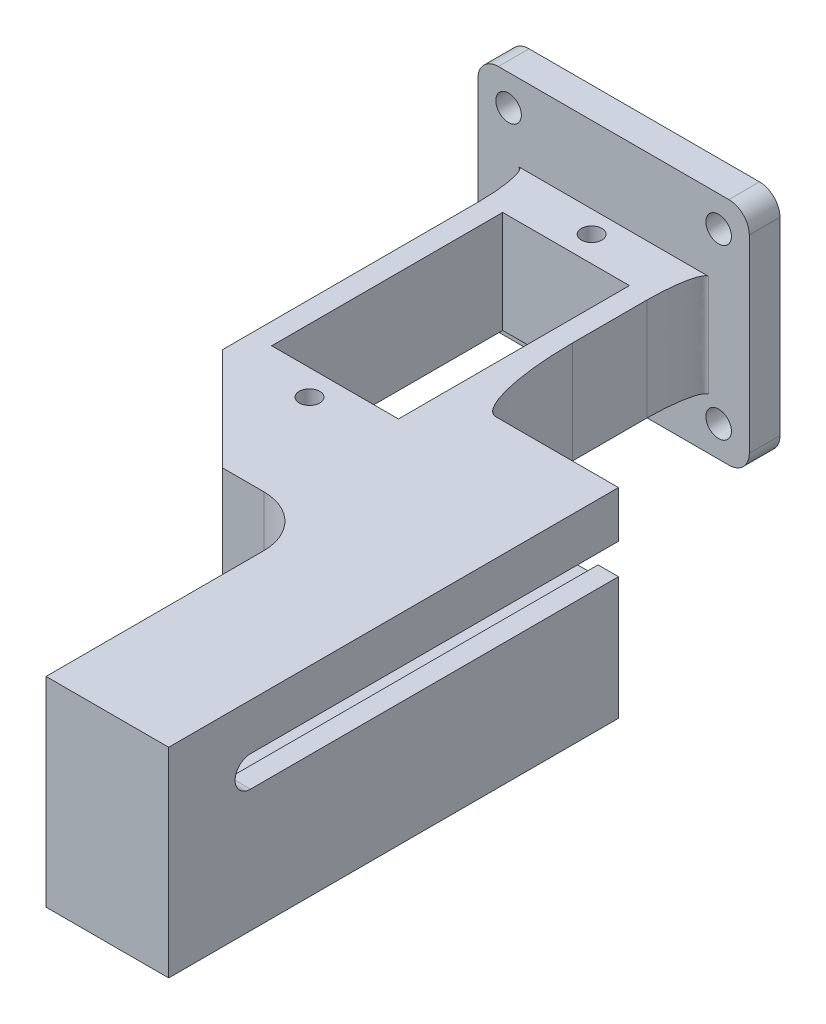
SolidWorks part; units mm, degrees
ref_plane "Front Plane" through (0, 0, 0) normal (0, 0, 1) x (1, 0, 0)
ref_plane "Top Plane" through (0, 0, 0) normal (0, 1, 0) x (1, 0, 0)
ref_plane "Right Plane" through (0, 0, 0) normal (1, 0, 0) x (0, 0, -1)
sketch "Sketch1" plane through (0, 0, 0) normal (0, 0, 1) x (1, 0, 0)
  line L0 (0, 11.25) -> (0, -11.25) construction
  line L1 (-13.275, 0) -> (13.275, 0) construction
  line L2 (-13.275, 9.25) -> (-11.275, 9.25) construction
  line L3 (-11.275, 9.25) -> (-11.275, 11.25) construction
  line L4 (11.275, 11.25) -> (11.275, 9.25) construction
  line L5 (11.275, 9.25) -> (13.275, 9.25) construction
  line L6 (11.275, -11.25) -> (11.275, -9.25) construction
  line L7 (11.275, -9.25) -> (13.275, -9.25) construction
  line L8 (13.275, -9.25) -> (13.275, 9.25)
  line L9 (11.275, 11.25) -> (-11.275, 11.25)
  line L10 (-13.275, 9.25) -> (-13.275, -9.25)
  line L11 (-11.275, -11.25) -> (11.275, -11.25)
  line L12 (-13.275, -9.25) -> (-11.275, -9.25) construction
  line L13 (-11.275, -9.25) -> (-11.275, -11.25) construction
  circle A0 centre (-10.275, 8.25) radius 1.25
  circle A1 centre (10.275, 8.25) radius 1.25
  circle A2 centre (10.275, -8.25) radius 1.25
  circle A3 centre (-10.275, -8.25) radius 1.25
  arc A8 (11.275, -11.25) -> (13.275, -9.25) centre (11.275, -9.25) ccw
  arc A9 (13.275, 9.25) -> (11.275, 11.25) centre (11.275, 9.25) ccw
  arc A10 (-11.275, 11.25) -> (-13.275, 9.25) centre (-11.275, 9.25) ccw
  arc A11 (-13.275, -9.25) -> (-11.275, -11.25) centre (-11.275, -9.25) ccw
  point P15 (0, 0)
  dimension "D3" = 2
  dimension "D4" = 2
  dimension "D5" = 2
  dimension "D6" = 2
  dimension "D7" = 2.5
  dimension "D1" = 26.55
  dimension "D2" = 22.5
  dimension "D8" = 3
  dimension "D9" = 3
extrude "Boss-Extrude1" add sketch "Sketch1" along normal blind 3
sketch "Sketch2" plane through (0, 0, 0) normal (0, 0, -1) x (-1, 0, 0)
  line L0 (11.275, -11.25) -> (-11.275, -11.25) construction
  line L1 (-8.275, 3.75) -> (8.275, 3.75)
  line L2 (-8.275, 3.75) -> (-8.275, -6.25)
  line L3 (-8.275, -6.25) -> (8.275, -6.25)
  line L4 (8.275, 3.75) -> (8.275, -6.25)
  line L5 (-8.275, 3.75) -> (8.275, -6.25) construction
  line L6 (-8.275, -6.25) -> (8.275, 3.75) construction
  line L7 (13.275, 9.25) -> (13.275, -9.25) construction
  point P0 (0, -1.25)
  dimension "D1" = 16.55
  dimension "D2" = 10
  dimension "D3" = 5
  dimension "D4" = 5
extrude "Boss-Extrude2" add sketch "Sketch2" along normal blind 30
sketch "Sketch3" plane through (0, 3.75, 0) normal (0, 1, 0) x (1, 0, 0)
  line L0 (-8.275, 30) -> (1.725, 40)
  line L1 (1.725, 40) -> (8.275, 40)
  line L2 (8.275, 40) -> (8.275, 30)
  line L3 (8.275, 30) -> (-8.275, 30)
  line L4 (8.275, 30) -> (8.275, 0) construction
  dimension "D1" = 10
  dimension "D2" = 45
  dimension "D3" = 6.55
extrude "Boss-Extrude3" add sketch "Sketch3" against normal up to surface (10 mm away) up to face at (0, -6.25, -15)
ref_plane "Plane1" through (0, 0, 1.5) normal (0, 0, 1) x (1, 0, 0)
mirror "Mirror1" about plane through (0, 0, 1.5) normal (0, 0, 1) of "Boss-Extrude3", "Boss-Extrude2"
sketch "Sketch4" plane through (0, -6.25, 0) normal (0, -1, 0) x (1, 0, 0)
  line L5 (8.275, 0) -> (-8.275, 0)
  line L6 (-8.275, 0) -> (-8.275, -30)
  line L7 (-8.275, -30) -> (1.725, -40)
  line L8 (1.725, -40) -> (8.275, -40)
  line L9 (8.275, -40) -> (8.275, 0)
  line L10 (8.275, 0) -> (-8.275, 0)
  line L11 (-8.275, 0) -> (-8.275, -30)
  line L12 (-8.275, -30) -> (1.725, -40)
  line L13 (1.725, -40) -> (8.275, -40)
  line L14 (8.275, -40) -> (8.275, 0)
  dimension "D1" = 0
extrude "Cut-Extrude1" cut sketch "Sketch4" against normal through all
ref_plane "Plane2" through (0, 0, 25.3) normal (0, 0, 1) x (1, 0, 0)
sketch "Sketch6" plane through (0, 0, 25.3) normal (0, 0, 1) x (1, 0, 0)
  line L0 (10.775, 3.75) -> (10.775, -15.8)
  line L1 (10.775, 3.75) -> (22.775, 3.75)
  line L2 (22.775, -15.8) -> (22.775, 3.75)
  line L12 (14.775, -15.8) -> (10.775, -15.8)
  line L13 (14.775, -13.8) -> (14.775, -15.8)
  line L14 (12.775, -13.8) -> (14.775, -13.8)
  line L15 (12.775, -7.8) -> (12.775, -13.8)
  line L16 (20.775, -7.8) -> (12.775, -7.8)
  line L17 (20.775, -13.8) -> (20.775, -7.8)
  line L18 (18.775, -13.8) -> (20.775, -13.8)
  line L19 (18.775, -15.8) -> (18.775, -13.8)
  line L20 (22.775, -15.8) -> (18.775, -15.8)
  line L21 (1.725, 3.75) -> (-8.275, 3.75) construction
  line L23 (8.275, -6.25) -> (8.275, 3.75) construction
  circle A1 centre (16.775, -2.3) radius 4
  point P3 (17.0855, -2.3)
  dimension "D8" = 6
  dimension "D2" = 8
  dimension "D1" = 12
  dimension "D3" = 6
  dimension "D4" = 6.05
  dimension "D5" = 19.55
  dimension "D6" = 8
  dimension "D7" = 6
  dimension "D9" = 2
  dimension "D10" = 2
  dimension "D11" = 19.55
  dimension "D12" = 4
  dimension "D13" = 4
  dimension "D14" = 2
  dimension "D15" = 2
  dimension "D16" = 0
  dimension "D17" = 2.5
  dimension "D18" = 4
extrude "Boss-Extrude4" add sketch "Sketch6" along normal blind 40
sketch "Sketch7" plane through (0, 3.75, 0) normal (0, 1, 0) x (1, 0, 0)
  line L0 (0, -3) -> (0, -5.15) construction
  line L1 (-8.275, -3) -> (8.275, -3) construction
  line L2 (0, -5.15) -> (0, -32.75) construction
  circle A0 centre (0, -5.15) radius 1
  circle A1 centre (0, -32.75) radius 1
  dimension "D3" = 2
  dimension "D4" = 2
  dimension "D1" = 2.15
  dimension "D2" = 27.6
extrude "Cut-Extrude2" cut sketch "Sketch7" against normal through all
sketch "Sketch8" plane through (0, -6.25, 0) normal (0, -1, 0) x (1, 0, 0)
  line L0 (0, 32.75) -> (0, 30.25) construction
  line L2 (-6.2, 30.25) -> (6.2, 30.25)
  line L3 (-6.2, 30.25) -> (-6.2, 7.65)
  line L4 (-6.2, 7.65) -> (6.2, 7.65)
  line L5 (6.2, 30.25) -> (6.2, 7.65)
  point P9 (0, 30.25)
  dimension "D1" = 2.5
  dimension "D2" = 22.6
  dimension "D3" = 12.4
extrude "Cut-Extrude3" cut sketch "Sketch8" against normal through all
sketch "Sketch9" plane through (8.275, 0, 0) normal (1, 0, 0) x (0, 0, -1)
  line L0 (-25.3, -15.8) -> (-25.3, 3.75) construction
  line L1 (-25.3, -6.25) -> (-25.3, 3.75)
  line L4 (-3, -6.25) -> (-3, 3.75)
  line L5 (-3, 3.75) -> (-43, 3.75)
  line L6 (-43, 3.75) -> (-43, -6.25)
  line L7 (-43, -6.25) -> (-3, -6.25)
  line L9 (-25.3, 3.75) -> (-43, 3.75)
  line L10 (-43, 3.75) -> (-43, -6.25)
  line L11 (-43, -6.25) -> (-25.3, -6.25)
  dimension "D1" = 0
extrude "Boss-Extrude5" add sketch "Sketch9" along normal up to surface (2.5 mm away) up to face at (10.775, -6.025, 45.3)
fillet "Fillet2" radius 5 1 edges at (10.775, -1.25, 43)
fillet "Fillet5" radius 2.5 1 edges at (10.775, -6.25, 36.65)
fillet "Fillet6" radius 10 1 edges at (8.275, -1.25, 25.3) second distance 2.5 first distance on face at (8.275, -1.25, 14.15)
fillet "Fillet7" radius 5 2 edges at (-8.275, -1.25, 3) (8.275, -1.25, 3) second distance 1 first distance on face at (-8.275, -1.25, 18) first distance on face at (8.275, 0, 12.225)
sketch "Sketch10" plane through (0, 0, 65.3) normal (0, 0, 1) x (1, 0, 0)
  line L0 (20.775, -7.8) -> (20.775, -13.8) construction
  line L1 (12.775, 0.2) -> (20.775, 0.2)
  line L2 (12.775, 0.2) -> (12.775, -4.8)
  line L3 (12.775, -4.8) -> (20.775, -4.8)
  line L4 (20.775, 0.2) -> (20.775, -4.8)
  line L5 (12.775, 0.2) -> (20.775, -4.8) construction
  line L6 (12.775, -4.8) -> (20.775, 0.2) construction
  point P0 (16.775, -2.3)
  dimension "D2" = 5
extrude "Cut-Extrude4" cut sketch "Sketch10" against normal up to surface (40 mm away) up to face at (16.775, -10.6135, 25.3)
sketch "Sketch11" plane through (0, 0, 25.3) normal (0, 0, -1) x (-1, 0, 0)
  line L1 (-19.8975, 0.2) -> (-13.6525, 0.2)
  line L3 (-19.8975, -4.8) -> (-13.6525, -4.8)
  arc A0 (-19.8975, -4.8) -> (-13.6525, -4.8) centre (-16.775, -2.3) ccw construction
  arc A1 (-13.6525, 0.2) -> (-19.8975, 0.2) centre (-16.775, -2.3) ccw construction
  arc A2 (-19.8975, -4.8) -> (-13.6525, -4.8) centre (-16.775, -2.3) ccw
  arc A3 (-13.6525, 0.2) -> (-19.8975, 0.2) centre (-16.775, -2.3) ccw
extrude "Boss-Extrude6" add sketch "Sketch11" against normal up to surface (40 mm away) up to face at (16.775, -10.5417, 65.3)
sketch "Sketch12" plane through (0, 0, 25.3) normal (0, 0, -1) x (-1, 0, 0)
  line L0 (-16.775, 0.2) -> (-16.775, -7.8) construction
  line L1 (-20.775, 0.2) -> (-12.775, 0.2) construction
  line L2 (-12.775, -7.8) -> (-20.775, -7.8) construction
  line L3 (-12.775, -4.8) -> (-20.775, -4.8) construction
  line L4 (-18.275, -4.8) -> (-15.275, -4.8)
  line L5 (-18.275, -4.8) -> (-18.275, -7.8)
  line L6 (-18.275, -7.8) -> (-15.275, -7.8)
  line L7 (-15.275, -4.8) -> (-15.275, -7.8)
  dimension "D1" = 3
extrude "Cut-Extrude5" cut sketch "Sketch12" against normal through all both and the other way through all
sketch "Sketch13" plane through (20.775, 0, 0) normal (-1, 0, 0) x (0, 0, 1)
  line L0 (45.3, 0.2) -> (45.3, -4.8) construction
  line L1 (25.3, 0.2) -> (65.3, 0.2) construction
  line L2 (65.3, -4.8) -> (25.3, -4.8) construction
  line L3 (61.3, -2.3) -> (29.3, -2.3) construction
  line L4 (61.3, -3.8) -> (29.3, -3.8)
  line L5 (61.3, -0.8) -> (29.3, -0.8)
  line L6 (25.3, -4.8) -> (25.3, 0.2) construction
  arc A0 (61.3, -3.8) -> (61.3, -0.8) centre (61.3, -2.3) ccw
  arc A1 (29.3, -0.8) -> (29.3, -3.8) centre (29.3, -2.3) ccw
  point P8 (45.3, -2.3)
  point P15 (27.8, -2.3)
  dimension "D1" = 2.5
  dimension "D2" = 3
extrude "Cut-Extrude6" cut sketch "Sketch13" against normal through all
sketch "Sketch16" plane through (22.775, 0, 0) normal (1, 0, 0) x (0, 0, -1)
  line L0 (-25.3, -8.75) -> (-25.3, 3.75) construction
  line L1 (-29.3, -0.8) -> (-25.3, -0.8)
  line L2 (-29.3, -0.8) -> (-29.3, -3.8)
  line L3 (-29.3, -3.8) -> (-25.3, -3.8)
  line L4 (-25.3, -0.8) -> (-25.3, -3.8)
  line L5 (-29.3, -3.8) -> (-61.3, -3.8) construction
extrude "Cut-Extrude7" cut sketch "Sketch16" against normal up to surface (2 mm away) up to face at (20.775, -2.3, 45.3)
sketch "Sketch17" plane through (0, 0, 65.3) normal (0, 0, 1) x (1, 0, 0)
  line L20 (20.775, -4.8) -> (18.275, -4.8)
  line L21 (18.275, -4.8) -> (18.275, -7.8)
  line L22 (18.275, -7.8) -> (20.775, -7.8)
  line L23 (20.775, -7.8) -> (20.775, -13.8)
  line L24 (20.775, -13.8) -> (18.775, -13.8)
  line L25 (18.775, -13.8) -> (18.775, -15.8)
  line L26 (18.775, -15.8) -> (22.775, -15.8)
  line L27 (22.775, -15.8) -> (22.775, 3.75)
  line L28 (22.775, 3.75) -> (10.775, 3.75)
  line L29 (10.775, 3.75) -> (10.775, -15.8)
  line L30 (10.775, -15.8) -> (14.775, -15.8)
  line L31 (14.775, -15.8) -> (14.775, -13.8)
  line L32 (14.775, -13.8) -> (12.775, -13.8)
  line L33 (12.775, -13.8) -> (12.775, -7.8)
  line L34 (12.775, -7.8) -> (15.275, -7.8)
  line L35 (15.275, -7.8) -> (15.275, -4.8)
  line L36 (15.275, -4.8) -> (12.775, -4.8)
  line L37 (12.775, -4.8) -> (12.775, 0.2)
  line L38 (12.775, 0.2) -> (20.775, 0.2)
  line L39 (20.775, 0.2) -> (20.775, -4.8)
  line L40 (20.775, -4.8) -> (18.275, -4.8)
  line L41 (18.275, -4.8) -> (18.275, -7.8)
  line L42 (18.275, -7.8) -> (20.775, -7.8)
  line L43 (20.775, -7.8) -> (20.775, -13.8)
  line L44 (20.775, -13.8) -> (18.775, -13.8)
  line L45 (18.775, -13.8) -> (18.775, -15.8)
  line L46 (18.775, -15.8) -> (22.775, -15.8)
  line L47 (22.775, -15.8) -> (22.775, 3.75)
  line L48 (22.775, 3.75) -> (10.775, 3.75)
  line L49 (10.775, 3.75) -> (10.775, -15.8)
  line L50 (10.775, -15.8) -> (14.775, -15.8)
  line L51 (14.775, -15.8) -> (14.775, -13.8)
  line L52 (14.775, -13.8) -> (12.775, -13.8)
  line L53 (12.775, -13.8) -> (12.775, -7.8)
  line L54 (12.775, -7.8) -> (15.275, -7.8)
  line L55 (15.275, -7.8) -> (15.275, -4.8)
  line L56 (15.275, -4.8) -> (12.775, -4.8)
  line L57 (12.775, -4.8) -> (12.775, 0.2)
  line L58 (12.775, 0.2) -> (20.775, 0.2)
  line L59 (20.775, 0.2) -> (20.775, -4.8)
  dimension "D1" = 0
extrude "Boss-Extrude7" add sketch "Sketch17" along normal blind 4
sketch "Sketch18" plane through (0, 0, 69.3) normal (0, 0, 1) x (1, 0, 0)
  line L1 (10.775, 3.75) -> (22.775, 3.75)
  line L2 (10.775, 3.75) -> (10.775, -15.8)
  line L3 (10.775, -15.8) -> (22.775, -15.8)
  line L4 (22.775, 3.75) -> (22.775, -15.8)
extrude "Boss-Extrude8" add sketch "Sketch18" against normal blind 2
